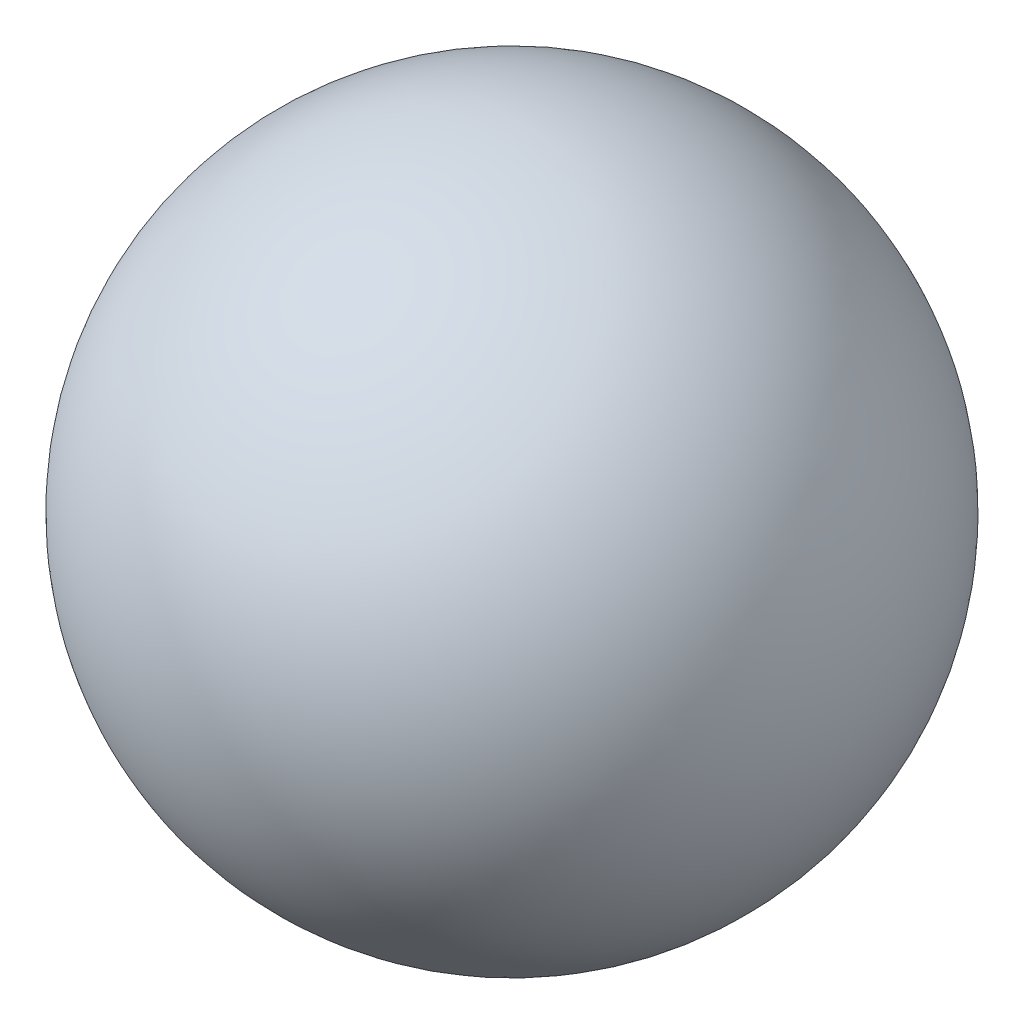
SolidWorks part; units mm, degrees
ref_plane "Front Plane" through (0, 0, 0) normal (0, 0, 1) x (1, 0, 0)
ref_plane "Top Plane" through (0, 0, 0) normal (0, 1, 0) x (1, 0, 0)
ref_plane "Right Plane" through (0, 0, 0) normal (1, 0, 0) x (0, 0, -1)
sketch "Sketch1" plane through (0, 0, 0) normal (0, 1, 0) x (1, 0, 0)
  line L0 (0, 6.35) -> (0, -6.35)
  arc A0 (0, 6.35) -> (0, -6.35) centre (0, 0) ccw
  dimension "D1" = 12.7
ref_axis "Axis1" through (0, 0, 3.4925) along (0, 0, -1)
revolve "Revolve3" add sketch "Sketch1" angle 360 about L0
